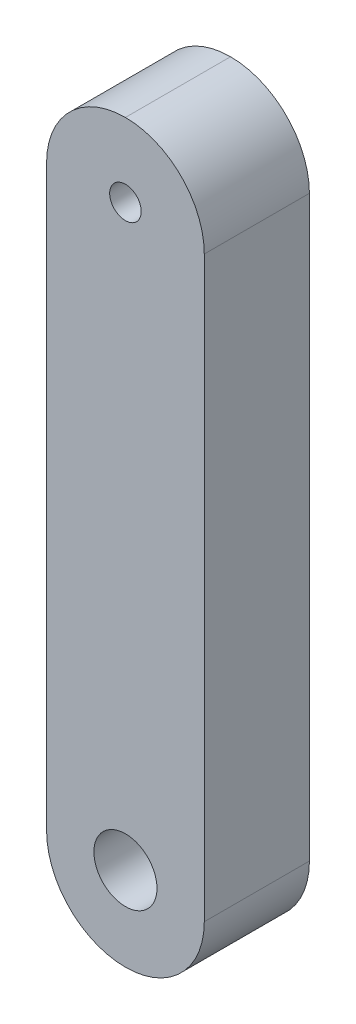
SolidWorks part; units mm, degrees
ref_plane "Front" through (0, 0, 0) normal (0, 0, 1) x (1, 0, 0)
ref_plane "Top" through (0, 0, 0) normal (0, 1, 0) x (1, 0, 0)
ref_plane "Right" through (0, 0, 0) normal (1, 0, 0) x (0, 0, -1)
sketch "Esquisse1" plane through (0, 0, 0) normal (0, 0, 1) x (1, 0, 0)
  line L1 (0, 0) -> (15, 0)
  line L2 (0, 0) -> (0, 70)
  line L3 (0, 70) -> (15, 70)
  line L4 (15, 0) -> (15, 70)
  dimension "D1" = 15
  dimension "D2" = 70
extrude "Boss.-Extru.1" add sketch "Esquisse1" along normal blind 10
sketch "Esquisse2" plane through (0, 0, 10) normal (0, 0, 1) x (1, 0, 0)
  line L0 (7.5, 63) -> (7.5, 70) construction
  line L1 (15, 70) -> (0, 70) construction
  line L2 (0, 0) -> (15, 0) construction
  line L3 (7.5, 8) -> (7.5, 0) construction
  circle A1 centre (7.5, 63) radius 1.5
  circle A2 centre (7.5, 8) radius 3
  point P11 (7.5, 0)
  dimension "D2" = 7
  dimension "D3" = 3
  dimension "D4" = 6
  dimension "D5" = 8
extrude "Enlèv. mat.-Extru.1" cut sketch "Esquisse2" against normal up to vertex (10 mm away) up to point (0, 70, 0)
fillet "Congé1" radius 7.5 4 edges at (15, 70, 5) (0, 70, 5) (15, 0, 5) (0, 0, 5)
